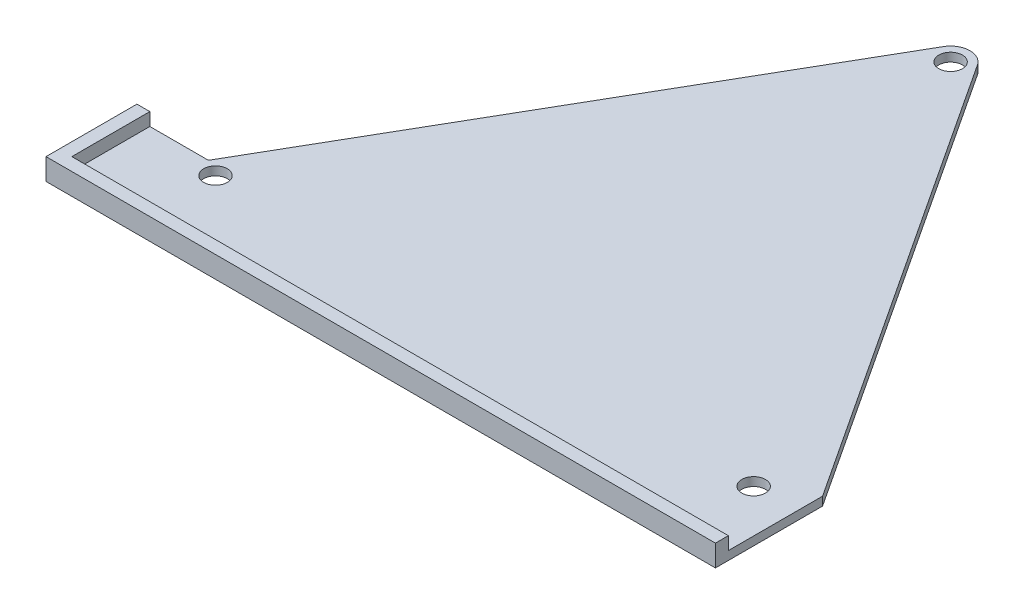
SolidWorks part; units mm, degrees
ref_plane "Front Plane" through (0, 0, 0) normal (0, 0, 1) x (1, 0, 0)
ref_plane "Top Plane" through (0, 0, 0) normal (0, 1, 0) x (1, 0, 0)
ref_plane "Right Plane" through (0, 0, 0) normal (1, 0, 0) x (0, 0, -1)
sketch "Sketch1" plane through (0, 0, 0) normal (0, 1, 0) x (1, 0, 0)
  line L0 (-62.5, -54.1266) -> (0, 54.1266) construction
  line L1 (0, 54.1266) -> (62.5, -54.1266) construction
  line L2 (62.5, -54.1266) -> (-62.5, -54.1266) construction
  line L5 (-3.8971, 56.3766) -> (-66.3971, -51.8766)
  line L6 (72.5, -48.1157) -> (3.8971, 56.3766)
  line L11 (-83, -73) -> (72.5, -73)
  line L17 (0, 54.1266) -> (0, 70) construction
  line L18 (0, -54.1266) -> (0, -70) construction
  line L19 (-83, -73) -> (72.5, -73)
  line L38 (-66.3971, -51.8766) -> (-80, -51.8766)
  line L39 (-80, -51.8766) -> (-83, -51.8766)
  line L40 (-83, -51.8766) -> (-83, -73)
  line L41 (72.5, -70) -> (-80, -70)
  line L42 (-80, -51.8766) -> (-80, -70)
  line L44 (72.5, -73) -> (72.5, -70)
  line L45 (72.5, -48.1157) -> (72.5, -70)
  line L49 (-80, -70) -> (80, -70) construction
  line L50 (-80, -70) -> (-80, 70) construction
  line L51 (-80, 70) -> (80, 70) construction
  line L52 (80, -70) -> (80, 70) construction
  line L53 (-80, -70) -> (80, 70) construction
  line L54 (-80, 70) -> (80, -70) construction
  circle A0 centre (0, -18.0422) radius 36.0844 construction
  arc A1 (3.8971, 56.3766) -> (-3.8971, 56.3766) centre (0, 54.1266) ccw
  circle A4 centre (0, 54.1266) radius 2.75
  circle A5 centre (62.5, -54.1266) radius 2.75
  circle A6 centre (-62.5, -54.1266) radius 2.75
  point P3 (-66.3971, -46.7217)
  point P10 (0, 0)
  point P15 (0, 0)
  point P31 (0, 70)
  dimension "D2" = 9
  dimension "D5" = 160
  dimension "D7" = 5.5
  dimension "D1" = 125
  dimension "D3" = 120
  dimension "D8" = 140
  dimension "D6" = 10
  dimension "D4" = 3
extrude "Boss-Extrude4" add sketch "Sketch1" along normal blind 2 contours L6 A1 L5 L38 L45 A6 A5 A4 region at (1.0917, 0, 25.8463)
extrude "Boss-Extrude7" add sketch "Sketch1<6>" along normal blind 5 contours L11 L44 L39 L40 region at (-13.2092, 0, 70.3975)
sketch "Sketch1<6>" plane through (0, 0, 0) normal (0, 1, 0) x (1, 0, 0) same geometry as "Sketch1"
